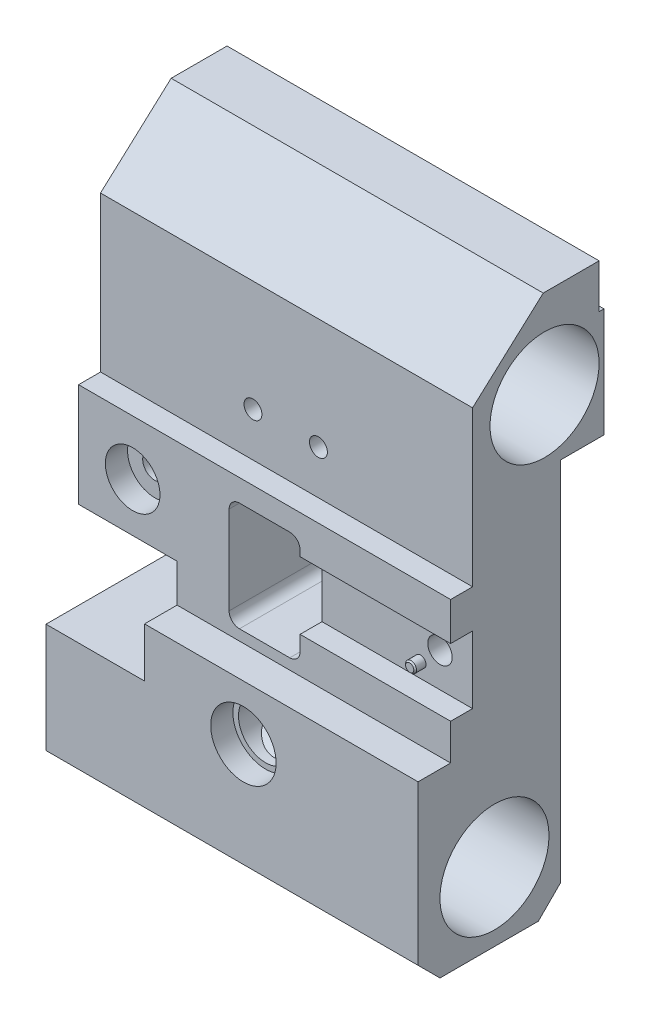
SolidWorks part; units mm, degrees
material "1060 Alloy"
ref_plane "Front Plane" through (0, 0, 0) normal (0, 0, 1) x (1, 0, 0)
ref_plane "Top Plane" through (0, 0, 0) normal (0, 1, 0) x (1, 0, 0)
ref_plane "Right Plane" through (0, 0, 0) normal (1, 0, 0) x (0, 0, -1)
sketch "Sketch1" plane through (0, 0, 0) normal (1, 0, 0) x (0, 0, -1)
  line L0 (14.15, 137.2) -> (30.37, 137.2)
  line L1 (30.37, 137.2) -> (30.37, 124.41)
  line L2 (30.37, 124.41) -> (31.79, 124.41)
  line L3 (31.79, 124.41) -> (31.79, 92.72)
  line L4 (31.79, 92.72) -> (19.1, 92.72)
  line L5 (19.1, 92.72) -> (19.1, -13.636)
  line L6 (19.1, -13.636) -> (12.736, -20)
  line L7 (12.736, -20) -> (-15.816, -20)
  line L8 (-15.816, -20) -> (-22.18, -13.636)
  line L9 (-22.18, -13.636) -> (-22.18, 32.5)
  line L10 (-22.18, 32.5) -> (-12.73, 32.5)
  line L11 (-12.73, 32.5) -> (-12.73, 73.61)
  line L12 (-12.73, 73.61) -> (-6.36, 73.61)
  line L13 (-6.36, 73.61) -> (-6.36, 118.61)
  line L14 (-6.36, 118.61) -> (14.15, 137.2)
  line L15 (-22.18, 32.5) -> (-22.18, 137.2) construction
  line L16 (-22.18, 137.2) -> (14.15, 137.2) construction
  line L17 (30.37, 137.2) -> (31.79, 137.2) construction
  line L18 (31.79, 137.2) -> (31.79, 124.41) construction
  line L19 (31.79, 92.72) -> (31.79, -20) construction
  line L20 (31.79, -20) -> (12.736, -20) construction
  line L21 (-22.18, -13.636) -> (-22.18, -20) construction
  line L22 (-22.18, -20) -> (-15.816, -20) construction
  line L23 (-22.18, 0) -> (31.79, 0) construction
  line L24 (0, -20) -> (0, 17.0401) construction
  line L25 (-22.18, -13.636) -> (19.1, -13.636) construction
  line L26 (0, -15.83) -> (46.0148, -15.83) construction
  line L27 (15.83, 0) -> (15.83, 26.825) construction
  line L28 (0, 15.83) -> (31.79, 15.83) construction
  line L29 (14.54, 111.46) -> (48.8082, 111.46) construction
  line L30 (14.54, 127.29) -> (58.4666, 127.29) construction
  line L31 (14.54, 95.63) -> (54.0932, 95.63) construction
  line L32 (30.37, 124.41) -> (30.37, 97.4751) construction
  line L33 (-15.83, 0) -> (-15.83, 21.2691) construction
  circle A0 centre (0, 0) radius 15.83
  circle A1 centre (14.54, 111.46) radius 15.83
  dimension "D14" = 31.66
  dimension "D1" = 41.28
  dimension "D2" = 38.15
  dimension "D3" = 157.2
  dimension "D4" = 44.48
  dimension "D5" = 2.84
  dimension "D6" = 31.69
  dimension "D7" = 25.46
  dimension "D8" = 31.83
  dimension "D9" = 52.5
  dimension "D10" = 93.61
  dimension "D11" = 9
  dimension "D12" = 9.91
  dimension "D13" = 16.22
  dimension "D15" = 45
  dimension "D16" = 3.27
  dimension "D17" = 6.35
  dimension "D18" = 4.17
extrude "Boss-Extrude1" add sketch "Sketch1" along normal blind 54 and the other way blind 54
sketch "Sketch2" plane through (0, 0, -19.1) normal (0, 0, -1) x (-1, 0, 0)
  line L0 (54, -13.636) -> (54, 92.72) construction
  line L1 (-7.3, 67.2) -> (7.3, 67.2)
  line L2 (-10.3, 64.2) -> (-10.3, 38.6)
  line L3 (-7.3, 35.6) -> (7.3, 35.6)
  line L4 (10.3, 64.2) -> (10.3, 38.6)
  line L5 (54, 43.53) -> (25.4, 43.53)
  line L6 (54, 43.53) -> (54, 18.13)
  line L7 (54, 18.13) -> (25.4, 18.13)
  line L8 (25.4, 43.53) -> (25.4, 18.13)
  line L9 (-9.25, 86.37) -> (9.75, 86.37) construction
  line L10 (-10.3, 64.2) -> (-10.3, 67.2) construction
  line L11 (-10.3, 67.2) -> (-7.3, 67.2) construction
  line L12 (7.3, 67.2) -> (10.3, 67.2) construction
  line L13 (10.3, 67.2) -> (10.3, 64.2) construction
  line L14 (10.3, 38.6) -> (10.3, 35.6) construction
  line L15 (10.3, 35.6) -> (7.3, 35.6) construction
  line L16 (-7.3, 35.6) -> (-10.3, 35.6) construction
  line L17 (-10.3, 35.6) -> (-10.3, 38.6) construction
  line L18 (-54, -13.636) -> (-54, 92.72) construction
  line L19 (54, -20) -> (-54, -20) construction
  line L20 (54, 137.2) -> (-54, 137.2) construction
  line L21 (54, 137.2) -> (-54, 137.2) construction
  line L22 (-3.3, 16.595) -> (-3.3, 92.72) construction
  line L25 (54, 92.72) -> (-54, 92.72) construction
  line L26 (9.75, 86.37) -> (9.75, 92.72) construction
  line L27 (-9.25, 86.37) -> (-9.25, 92.72) construction
  line L28 (38.3, 57.72) -> (38.3, 92.72) construction
  line L29 (-44.55, 52.92) -> (-44.55, 92.72) construction
  circle A0 centre (-3.3, 16.595) radius 7.875
  circle A1 centre (-44.55, 52.92) radius 5.5 construction
  circle A2 centre (38.3, 57.72) radius 5.55 construction
  circle A3 centre (-9.25, 86.37) radius 2.6
  circle A4 centre (9.75, 86.37) radius 2.6
  circle A5 centre (-3.3, 16.595) radius 9.42 construction
  circle A6 centre (-9.25, 86.37) radius 4.425 construction
  circle A7 centre (9.75, 86.37) radius 4.425 construction
  circle A8 centre (38.3, 57.72) radius 3.525
  circle A9 centre (-44.55, 52.92) radius 3.55
  arc A10 (-7.3, 35.6) -> (-10.3, 38.6) centre (-7.3, 38.6) cw
  arc A11 (7.3, 35.6) -> (10.3, 38.6) centre (7.3, 38.6) ccw
  arc A12 (7.3, 67.2) -> (10.3, 64.2) centre (7.3, 64.2) cw
  arc A13 (-7.3, 67.2) -> (-10.3, 64.2) centre (-7.3, 64.2) ccw
  dimension "D1" = 3
  dimension "D17" = 18.84
  dimension "D18" = 15.75
  dimension "D20" = 8.85
  dimension "D21" = 5.2
  dimension "D22" = 7.05
  dimension "D23" = 11.1
  dimension "D24" = 7.1
  dimension "D25" = 11
  dimension "D2" = 43.7
  dimension "D3" = 43.7
  dimension "D4" = 55.6
  dimension "D5" = 70
  dimension "D6" = 38.13
  dimension "D7" = 25.4
  dimension "D8" = 28.6
  dimension "D9" = 15.7
  dimension "D10" = 44.25
  dimension "D11" = 63.25
  dimension "D12" = 9.45
  dimension "D13" = 50.7
  dimension "D14" = 35
  dimension "D15" = 6.35
  dimension "D16" = 39.8
  dimension "D19" = 76.125
extrude "Cut-Extrude1" cut sketch "Sketch2" against normal through all
sketch "Sketch3" plane through (0, 0, 12.73) normal (0, 0, 1) x (1, 0, 0)
  line L0 (54, 73.61) -> (54, 32.5) construction
  line L1 (54, 43) -> (10.3, 43)
  line L2 (54, 43) -> (54, 62.52)
  line L3 (54, 62.52) -> (10.3, 62.52)
  line L4 (10.3, 43) -> (10.3, 62.52)
  line L5 (10.3, 38.6) -> (10.3, 64.2) construction
  line L6 (-25.4, 32.5) -> (54, 32.5) construction
  dimension "D1" = 10.5
  dimension "D2" = 19.52
extrude "Cut-Extrude2" cut sketch "Sketch3" against normal blind 6.36
sketch "Sketch4" plane through (0, 0, 6.37) normal (0, 0, 1) x (1, 0, 0)
  line L0 (40.5, 47.335) -> (54, 47.335) construction
  line L2 (54, 43) -> (54, 62.52) construction
  line L3 (38.915, 48.92) -> (38.915, 62.52) construction
  line L4 (54, 62.52) -> (10.3, 62.52) construction
  circle A0 centre (38.915, 47.335) radius 1.585
  dimension "D1" = 3.17
  dimension "D2" = 13.5
  dimension "D3" = 13.6
extrude "Boss-Extrude2" add sketch "Sketch4" along normal blind 3.15
sketch "Sketch10" plane through (0, 0, -19.1) normal (0, 0, -1) x (-1, 0, 0)
  circle A1 centre (-38.915, 47.335) radius 1.585
  circle A2 centre (-38.915, 47.335) radius 1.585
  dimension "D1" = 0
extrude "Cut-Extrude6" cut sketch "Sketch10" against normal blind 20
sketch "Sketch11" plane through (0, 0, -19.1) normal (0, 0, -1) x (-1, 0, 0)
  circle A0 centre (38.3, 57.72) radius 5.5
  circle A1 centre (-44.55, 52.92) radius 5.42
  circle A2 centre (-9.25, 86.37) radius 4.55
  circle A3 centre (9.75, 86.37) radius 4.55
  circle M11 centre (38.3, 57.72) radius 3.525
  circle M12 centre (9.75, 86.37) radius 2.6
  circle M13 centre (-9.25, 86.37) radius 2.6
  dimension "D1" = 10.84
  dimension "D2" = 11
  dimension "D3" = 9.1
extrude "Cut-Extrude7" cut sketch "Sketch11" against normal blind 6.56 contours A0 M11 | A1 region at (-32.9556, 57.72, -19.1)
chamfer "Chamfer1" distance 0.4 angle 45 1 edges at (40.5, 47.335, 9.52)
sketch "Sketch5" plane through (0, 0, 12.73) normal (0, 0, 1) x (1, 0, 0)
  circle A0 centre (-38.3, 57.72) radius 7.925
  dimension "D1" = 15.85
extrude "Cut-Extrude3" cut sketch "Sketch5" against normal blind 6.44
sketch "Sketch6" plane through (0, 0, 22.18) normal (0, 0, 1) x (1, 0, 0)
  circle A0 centre (3.3, 16.595) radius 9.495
  dimension "D1" = 18.99
extrude "Cut-Extrude4" cut sketch "Sketch6" against normal blind 6.44
sketch "Sketch7" plane through (0, 0, -19.1) normal (0, 0, -1) x (-1, 0, 0)
  line L0 (25.4, 43.53) -> (25.4, 18.13) construction
  line L1 (25.4, 34.07) -> (16.63, 34.07)
  line L2 (25.4, 34.07) -> (25.4, -0.89)
  line L3 (25.4, -0.89) -> (16.63, -0.89)
  line L4 (16.63, 34.07) -> (16.63, -0.89)
  line L5 (54, 92.72) -> (-54, 92.72) construction
  dimension "D1" = 8.77
  dimension "D2" = 34.96
  dimension "D3" = 58.65
extrude "Boss-Extrude3" add sketch "Sketch7" along normal blind 3.1
sketch "Sketch8" plane through (0, 0, -22.2) normal (0, 0, -1) x (-1, 0, 0)
  line L0 (21.4, 3.82) -> (21.4, 92.72) construction
  line L1 (54, 92.72) -> (-54, 92.72) construction
  line L2 (16.63, -0.89) -> (25.4, -0.89) construction
  line L5 (25.4, -0.89) -> (25.4, 34.07) construction
  circle A0 centre (21.4, 29.135) radius 2
  circle A1 centre (21.4, 3.82) radius 2
  dimension "D2" = 4
  dimension "D1" = 4
  dimension "D3" = 4.71
  dimension "D4" = 30.025
extrude "Cut-Extrude5" cut sketch "Sketch8" against normal blind 15
extrude "Cut-Extrude8" cut sketch "Sketch11<3>" against normal blind 5.45 contours A2 M13 | A3 M12 region at (13.6713, 86.37, -19.1) region at (-5.3287, 86.37, -19.1)
sketch "Sketch11<3>" plane through (0, 0, -19.1) normal (0, 0, -1) x (-1, 0, 0) same geometry as "Sketch11"
sketch "Sketch12" plane through (0, 0, -19.1) normal (0, 0, -1) x (-1, 0, 0)
  circle A0 centre (-3.3, 16.595) radius 9.475
  dimension "D1" = 18.95
extrude "Cut-Extrude9" cut sketch "Sketch12" against normal blind 5.15
sketch "Sketch13" plane through (0, 0, -19.1) normal (0, 0, -1) x (-1, 0, 0)
  line L0 (-17.6348, 41.72) -> (20.3, 41.72) construction
  line L1 (-13.5, 41.72) -> (-13.5, 73.72) construction
  line L2 (13.2, 41.72) -> (13.2, 73.72) construction
  line L3 (-13.5, 73.72) -> (13.2, 73.72) construction
  line L4 (54, 92.72) -> (-54, 92.72) construction
  line L5 (-54, -13.636) -> (-54, 92.72) construction
  circle A0 centre (-13.5, 73.72) radius 2
  circle A1 centre (13.2, 73.72) radius 2
  circle A2 centre (-13.5, 41.72) radius 2
  circle A3 centre (13.2, 41.72) radius 2
  circle A4 centre (20.3, 41.72) radius 2
  circle A5 centre (-21, 41.92) radius 2
  circle A6 centre (21.4, 29.135) radius 2 construction
  dimension "D3" = 40.5
  dimension "D1" = 51
  dimension "D2" = 19
  dimension "D4" = 67.2
  dimension "D5" = 33
  dimension "D6" = 0.2
  dimension "D7" = 74.3
sketch "Sketch14" plane through (0, 0, -30.37) normal (0, 0, -1) x (-1, 0, 0)
  line L0 (-0.2, 130.91) -> (-0.2, 124.41) construction
  line L1 (54, 124.41) -> (-54, 124.41) construction
  line L2 (-0.2, 130.91) -> (-54, 130.91) construction
  line L3 (-54, 124.41) -> (-54, 137.2) construction
  circle A0 centre (-0.2, 130.91) radius 2
  circle A1 centre (13.2, 73.72) radius 2 construction
  dimension "D1" = 53.8
  dimension "D2" = 6.5
extrude "Cut-Extrude10" cut sketch "Sketch13" against normal blind 10
extrude "Cut-Extrude11" cut sketch "Sketch14" against normal blind 10
